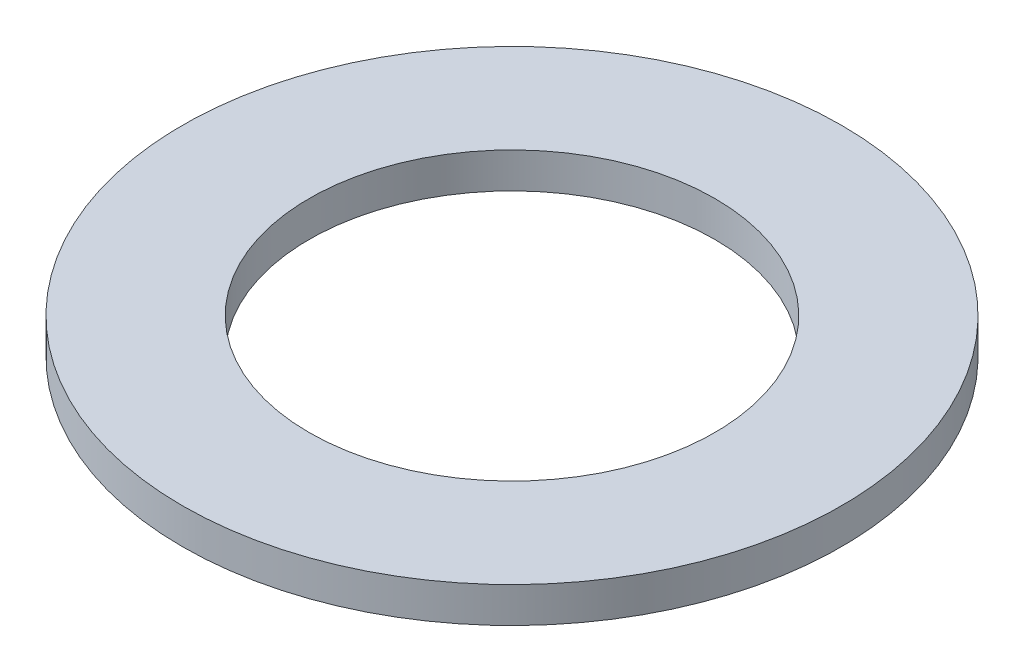
SolidWorks part; units mm, degrees
ref_plane "Front Plane" through (0, 0, 0) normal (0, 0, 1) x (1, 0, 0)
ref_plane "Top Plane" through (0, 0, 0) normal (0, 1, 0) x (1, 0, 0)
ref_plane "Right Plane" through (0, 0, 0) normal (1, 0, 0) x (0, 0, -1)
sketch "Sketch1" plane through (0, 0, 0) normal (0, 1, 0) x (1, 0, 0)
  circle A0 centre (0, 0) radius 65
  dimension "FLANGE_OD" = 130
extrude "Boss-Extrude1" add sketch "Sketch1" along normal blind 7
sketch "Sketch2" plane through (0, 0, 0) normal (0, 1, 0) x (1, 0, 0)
  circle A0 centre (0, 0) radius 40
  dimension "BORE_D" = 80
extrude "Cut-Extrude1" cut sketch "Sketch2" along normal through all
sketch "Sketch3" plane through (0, 7, 0) normal (0, 1, 0) x (1, 0, 0)
  circle A0 centre (0, 0) radius 26.7432 construction
  circle A1 centre (-26.7432, 0) radius 2.1494
  dimension "BOLT_D" = 4.2987
  dimension "BOLT_PCD" = 53.4863
extrude "Cut-Extrude2" cut sketch "Sketch3" against normal blind 5.0496 rebuild error yes
pattern_circular "CirPattern1" count 6 over 360 rebuild error yes
